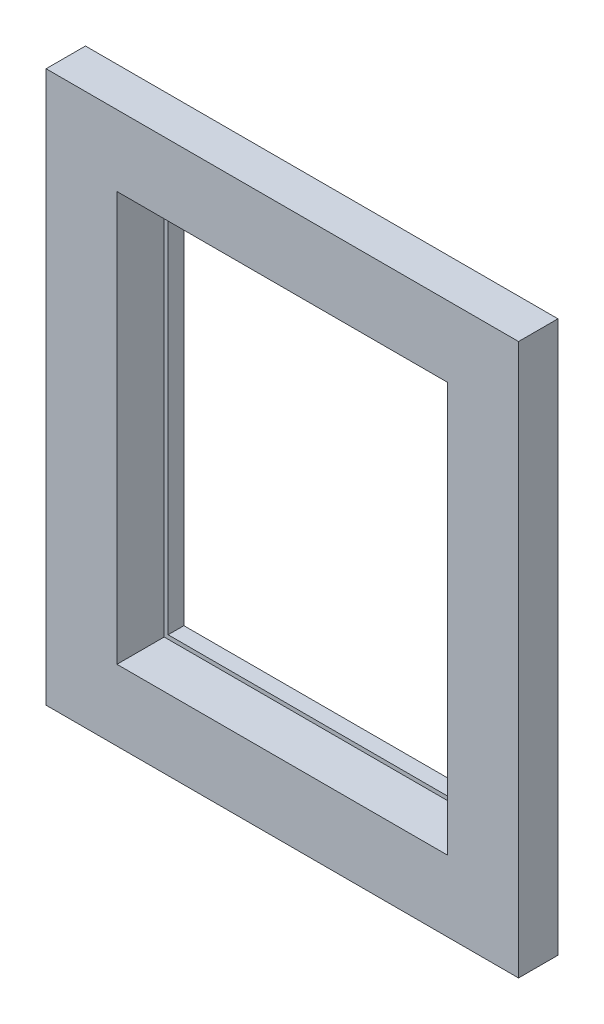
SolidWorks part; units mm, degrees
material "ABS"
ref_plane "Спереди" through (0, 0, 0) normal (0, 0, 1) x (1, 0, 0)
ref_plane "Сверху" through (0, 0, 0) normal (0, 1, 0) x (1, 0, 0)
ref_plane "Справа" through (0, 0, 0) normal (1, 0, 0) x (0, 0, -1)
sketch "Эскиз1" plane through (0, 0, 0) normal (0, 0, 1) x (1, 0, 0)
  line L5 (-30, -35) -> (30, -35)
  line L6 (-30, -35) -> (-30, 35)
  line L7 (-30, 35) -> (30, 35)
  line L8 (30, -35) -> (30, 35)
  line L9 (-30, -35) -> (30, 35) construction
  line L10 (-30, 35) -> (30, -35) construction
  line L11 (-20.5, -25.5) -> (20.5, -25.5)
  line L12 (-20.5, -25.5) -> (-20.5, 25.5)
  line L13 (-20.5, 25.5) -> (20.5, 25.5)
  line L14 (20.5, -25.5) -> (20.5, 25.5)
  line L15 (-20.5, -25.5) -> (20.5, 25.5) construction
  line L16 (-20.5, 25.5) -> (20.5, -25.5) construction
  point P0 (0, 0)
  point P5 (0, 0)
  dimension "D1" = 41
  dimension "D2" = 51
  dimension "D3" = 70
  dimension "D4" = 60
extrude "Бобышка-Вытянуть1" add sketch "Эскиз1" along normal blind 6 and the other way blind 2
sketch "Эскиз2" plane through (0, 0, 0) normal (0, 0, -1) x (-1, 0, 0)
  line L1 (-21, 26) -> (21, 26)
  line L2 (-21, 26) -> (-21, -26)
  line L3 (-21, -26) -> (21, -26)
  line L4 (21, 26) -> (21, -26)
  line L5 (-21, 26) -> (21, -26) construction
  line L6 (-21, -26) -> (21, 26) construction
  point P0 (0, 0)
  dimension "D1" = 52
  dimension "D2" = 42
extrude "Вырез-Вытянуть2" cut sketch "Эскиз2" against normal through all
sketch "Эскиз3" plane through (0, -35, 0) normal (0, -1, 0) x (-1, 0, 0)
  line L1 (-30, 2) -> (-26, 2)
  line L2 (-30, 2) -> (-30, -1)
  line L3 (-30, -1) -> (-26, -1)
  line L4 (-26, 2) -> (-26, -1)
  dimension "D1" = 4
  dimension "D2" = 3
sketch "Эскиз4" plane through (0, 0, -2) normal (0, 0, -1) x (-1, 0, 0)
  line L4 (-30, 35) -> (-30, -35)
  line L6 (-30, 35) -> (-30, -35)
  line L12 (-30, -35) -> (30, -35)
  line L14 (-30, -35) -> (30, -35)
  line L16 (30, -35) -> (30, 35)
  line L17 (30, -35) -> (30, 35)
  line L18 (30, 35) -> (-30, 35)
  line L19 (30, 35) -> (-30, 35)
  dimension "D1" = 0
sweep "Вырез-По траектории1" cut profiles "Эскиз3" path "Эскиз4"
chamfer "Фаска2" distance 3 angle 45 4 edges at (26, 0, -2) (0, 31, -2) (-26, 0, -2) (0, -31, -2)
